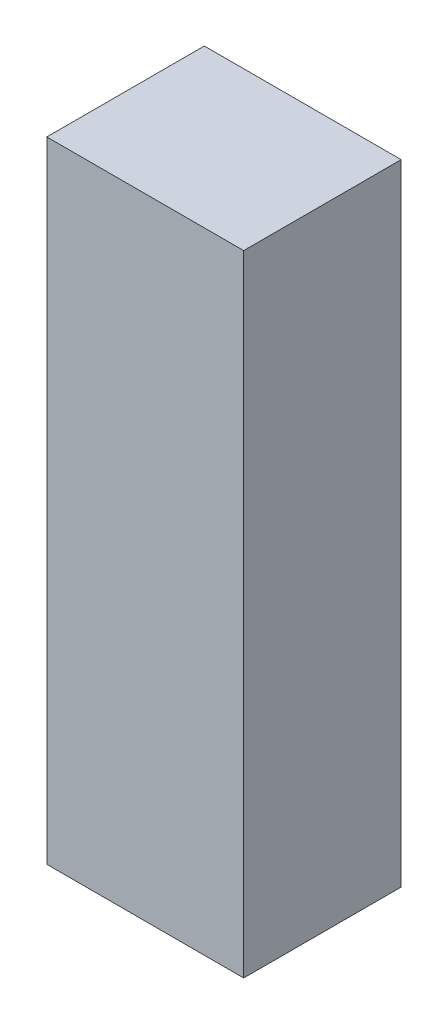
SolidWorks part; units mm, degrees
ref_plane "Front Plane" through (0, 0, 0) normal (0, 0, 1) x (1, 0, 0)
ref_plane "Top Plane" through (0, 0, 0) normal (0, 1, 0) x (1, 0, 0)
ref_plane "Right Plane" through (0, 0, 0) normal (1, 0, 0) x (0, 0, -1)
sketch "Sketch1" plane through (0, 0, 0) normal (0, 0, 1) x (1, 0, 0)
  line L1 (0, 0) -> (0.25, 0)
  line L2 (0, 0) -> (0, 0.8)
  line L3 (0, 0.8) -> (0.25, 0.8)
  line L4 (0.25, 0) -> (0.25, 0.8)
  dimension "D1" = 0.25
  dimension "D2" = 0.8
extrude "Boss-Extrude1" add sketch "Sketch1" along normal blind 0.2 contours L2 L3 L4 L1
equation "\"t\"= 0.25'thickness of the sheets"
equation "\"t_cf\"= 0.115'thickness of single carbon fiber layer"
equation "\"t_kapton\"= 0.025'thickness of single Kapton flex layer"
equation "\"t_fr4\"= 0.1'thickness of FR4 with copper layer"
equation "\"joint_flex\"= 0.1'Width of flextures gap"
equation "\"joint_flex_eff\"= 0.02'Width of flecture after castelation"
equation "\"joint_fold\"= 0.2'Width of folding joints for 90deg fold"
equation "\"gap_tolerance\"= 0.002'Width to have interfecence fit between carbon fiber inserts"
equation "\"assemble_angle\"= 90'Angle of assembly parts"
equation "\"link_lift\"= 0.5'Actuation linkage amplification for the lift motion"
equation "\"link_swing\"= 0.45'Actuation linkage amplification for the swing motion"
equation "\"D1@Sketch1\"=\"t\""
equation "\"D1@Boss-Extrude1\"=\"joint_fold\""
